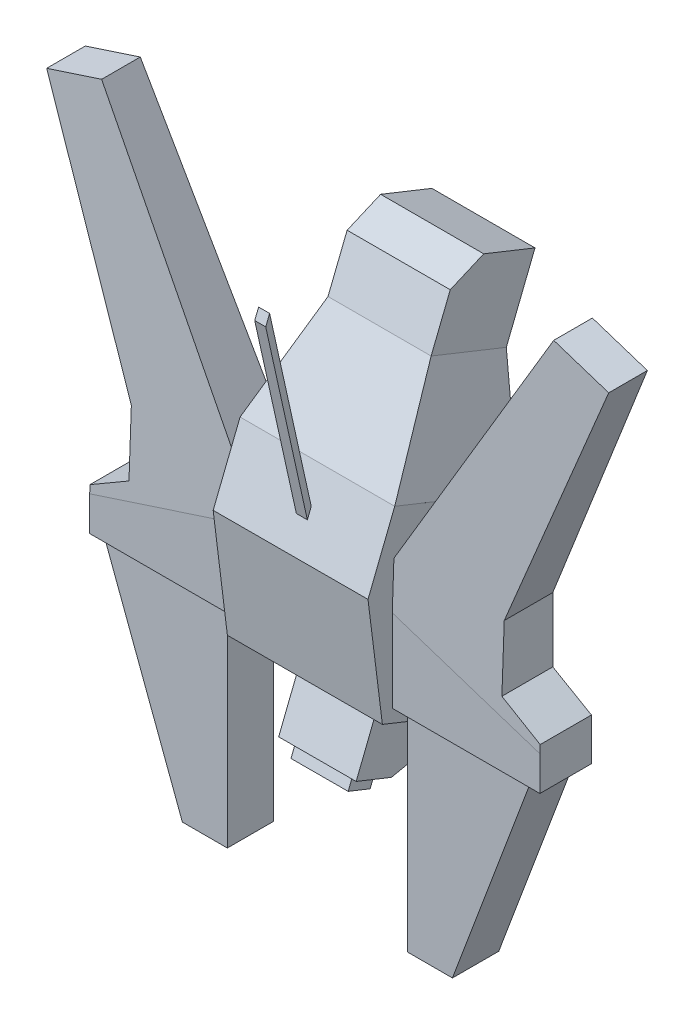
SolidWorks part; units mm, degrees
ref_plane "Front Plane" through (0, 0, 0) normal (0, 0, 1) x (1, 0, 0)
ref_plane "Top Plane" through (0, 0, 0) normal (0, 1, 0) x (1, 0, 0)
ref_plane "Right Plane" through (0, 0, 0) normal (1, 0, 0) x (0, 0, -1)
sketch "Sketch4" plane through (0, 0, 0) normal (0, 0, 1) x (1, 0, 0)
  line L0 (0, 0) -> (0, 12.7)
  line L1 (0, 12.7) -> (-14.6644, 38.1)
  line L2 (-14.6644, 38.1) -> (-20.0842, 36.3289)
  line L3 (-20.0842, 36.3289) -> (-10.7611, 12.7137)
  line L4 (-10.7611, 12.7137) -> (-10.7611, 6.3637)
  line L5 (-10.7611, 6.3637) -> (-14.5711, 4.164)
  line L6 (-14.5711, 4.164) -> (-14.5711, 0)
  line L7 (-14.5711, 0) -> (0, 0)
  dimension "D1" = 12.7
  dimension "D2" = 6.35
  dimension "D3" = 3.81
  dimension "D4" = 25.4
extrude "Boss-Extrude1" add sketch "Sketch4" along normal blind 5.08
chamfer "Chamfer5" distance 1.27 distance2 33.02 1 edges at (-17.3743, 37.2144, 5.08) first distance on face at (-17.3743, 37.2144, 2.54)
sketch "Sketch6" plane through (0, 0, 0) normal (0, -1, 0) x (1, 0, 0)
  line L0 (-7.2855, 0) -> (-7.2855, 5.08) construction
  line L1 (-14.5711, 0) -> (0, 0) construction
  line L2 (-14.5711, 5.08) -> (0, 5.08) construction
  line L4 (-13.312, 0.258) -> (-1.2591, 0.258)
  line L5 (-13.312, 0.258) -> (-13.312, 4.822)
  line L6 (-13.312, 4.822) -> (-1.2591, 4.822)
  line L7 (-1.2591, 0.258) -> (-1.2591, 4.822)
  line L8 (-13.312, 0.258) -> (-1.2591, 4.822) construction
  line L9 (-13.312, 4.822) -> (-1.2591, 0.258) construction
  point P6 (-7.2855, 2.54)
extrude "Boss-Extrude2" add sketch "Sketch6" along normal blind 20.32
chamfer "Chamfer6" distance 20.32 distance2 7.62 1 edges at (-13.312, -20.32, 2.54) first distance on face at (-13.312, -10.16, 2.54)
ref_plane "Plane2" through (7.62, 0, 0) normal (1, 0, 0) x (0, 0, -1)
mirror "Mirror8" about plane through (7.62, 0, 0) normal (1, 0, 0) of bodies 102
ref_axis "Axis2" through (7.62, 4.164, 0) along (0, -1, 0)
ref_plane "Plane4" through (0, 0, 0) normal (0, 0, 1) x (0, -1, 0)
sketch "Sketch7" plane through (0, 0, 0) normal (0, 0, 1) x (0, -1, 0)
  line L1 (5.0987, 0) -> (5.0987, 15.2803)
  line L4 (-20.2457, 15.24) -> (-20.2457, 0)
  line L6 (5.0987, 0) -> (-20.2457, 0)
  line L7 (-20.2457, 15.24) -> (5.0987, 15.2803)
extrude "Boss-Extrude5" add sketch "Sketch7" along normal mid plane 38.1 contours L1 L7 L4 L6
sketch "Sketch13" plane through (15.2721, 0.0243, 0) normal (1, 0.0016, 0) x (0, 0, -1)
  line L0 (-19.05, 4.2862) -> (4.4964, -5.1229)
  line L1 (-19.05, 20.2215) -> (-19.05, -5.1229) construction
  line L2 (-19.05, -5.1229) -> (19.05, -5.1229) construction
  line L3 (-19.05, 4.2862) -> (-19.05, -5.1229)
  line L4 (-19.05, -5.1229) -> (4.4964, -5.1229)
ref_plane "Plane6" through (0, -5.0987, 19.05) normal (1, 0, 0) x (0, 0, -1)
extrude "Cut-Extrude4" cut sketch "Sketch13" against normal blind 15.494 contours L3 L4 L0
sketch "Sketch18" plane through (0, -5.0987, 19.05) normal (1, 0, 0) x (0, 0, -1)
  line L0 (23.4857, 0) -> (0, 9.3849)
  line L1 (23.4857, 0) -> (33.6133, 25.3444)
  line L2 (0, 25.3444) -> (38.1, 25.3444) construction
  line L3 (23.4857, 0) -> (38.1, 0)
  line L4 (38.1, 0) -> (38.1, 25.3444)
  line L5 (38.1, 25.3444) -> (33.6133, 25.3444)
  dimension "D1" = 90
extrude "Cut-Extrude5" cut sketch "Sketch18" along normal blind 15.494 contours L4 L5 L1 L3 region at (0, 5.3338, -13.8273)
sketch "Sketch19" plane through (0, 0, 0) normal (-1, 0, 0) x (0, 0, 1)
  line L0 (19.05, 4.2863) -> (11.1889, 1.145)
  line L1 (-4.4357, -5.0987) -> (19.05, 4.2863) construction
  line L2 (19.05, 4.2863) -> (12.6726, 20.2457)
  line L3 (19.05, 20.2457) -> (-14.5633, 20.2457) construction
  line L4 (12.6726, 20.2457) -> (19.05, 20.2457)
  line L5 (19.05, 20.2457) -> (19.05, 4.2863)
  line M5 (19.05, 4.2863) -> (19.05, 20.2457)
  line M6 (19.05, 20.2457) -> (-14.5633, 20.2457)
  dimension "D1" = 90
extrude "Cut-Extrude6" cut sketch "Sketch19" against normal blind 15.494 contours L2 M5 M6 region at (0, 14.9259, 16.9242)
sketch "Sketch20" plane through (0, 0, 0) normal (-1, 0, 0) x (0, 0, 1)
  line L0 (12.6726, 20.2457) -> (16.227, 11.3507)
  line L1 (19.05, 4.2863) -> (12.6726, 20.2457) construction
  line L2 (12.6726, 20.2457) -> (-10.8131, 10.8608)
  line L3 (-4.4357, -5.0987) -> (-14.5633, 20.2457) construction
  line L4 (-10.8131, 10.8608) -> (-14.5633, 20.2457)
  line L5 (-14.5633, 20.2457) -> (12.6726, 20.2457)
  line M10 (12.6726, 20.2457) -> (-14.5633, 20.2457)
  line M11 (-14.5633, 20.2457) -> (-4.4357, -5.0987)
  dimension "D1" = 90
extrude "Cut-Extrude7" cut sketch "Sketch20" against normal blind 15.494 contours L2 M10 M11 region at (0, 17.1174, -4.2346)
chamfer "Chamfer7" distance 25.4 distance2 13.97 1 edges at (7.6327, 4.2967, 19.0458) first distance on face at (7.6263, 12.2712, 15.8592)
sketch "Sketch21" plane through (0, 0, 0) normal (-1, 0, 0) x (0, 0, 1)
  line L0 (8.4777, 18.5694) -> (4.8258, 17.1101)
  line L1 (8.4777, 18.5694) -> (-10.8131, 10.8608) construction
  line L2 (4.8258, 17.1101) -> (7.4791, 10.4703)
  line L3 (6.0774, -0.8976) -> (8.4777, 18.5694) construction
  line L4 (7.4791, 10.4703) -> (8.4777, 18.5694)
extrude "Cut-Extrude9" cut sketch "Sketch21" against normal blind 15.494 contours L4 L0 L2
sketch "Sketch22" plane through (0.0046, -2.8682, 1.1461) normal (0.0015, -0.9286, 0.3711) x (1, 0.0014, -0.0005)
  line L0 (15.2757, -6.011) -> (-0.0046, -6.011) construction
  line L11 (7.6356, -6.011) -> (11.537, -6.011)
  line L12 (11.537, -6.011) -> (11.537, 1.5466)
  line L13 (11.537, 1.5466) -> (3.9, 1.5466)
  line L14 (3.9, 1.5466) -> (3.9, -6.011)
  line L15 (3.9, -6.011) -> (7.6356, -6.011)
extrude "Boss-Extrude7" add sketch "Sketch22" along normal blind 6.35
sketch "Sketch24" plane through (0.0046, -2.8682, 1.1461) normal (0.0015, -0.9286, 0.3711) x (1, 0.0014, -0.0005)
  line L0 (11.537, -6.011) -> (11.537, 1.5466) construction
  line L1 (15.2757, -6.011) -> (11.537, -6.011)
  line L2 (15.2757, -6.011) -> (15.2757, -2.2322)
  line L3 (15.2757, -2.2322) -> (11.537, -2.2322)
  line L4 (11.537, -6.011) -> (11.537, -2.2322)
  line L5 (3.9, 1.5466) -> (3.9, -6.011) construction
  line L6 (-0.0046, -6.011) -> (3.9, -6.011)
  line L7 (-0.0046, -6.011) -> (-0.0046, -2.2322)
  line L8 (-0.0046, -2.2322) -> (3.9, -2.2322)
  line L9 (3.9, -6.011) -> (3.9, -2.2322)
extrude "Cut-Extrude11" cut sketch "Sketch24" against normal blind 19.05
chamfer "Chamfer9" distance 2.54 distance2 3.81 1 edges at (7.7324, -10.9847, -2.0836) first distance on face at (7.7151, -0.062, -6.4483)
sketch "Sketch25" plane through (0, 13.0913, -5.2313) normal (0, 0.9286, -0.3711) x (1, 0, 0)
  line L0 (11.5162, 6.011) -> (11.5162, 4.6398)
  line L1 (11.5162, 6.011) -> (11.5162, 2.2322) construction
  line L2 (11.5162, 4.6398) -> (3.8792, 4.6398)
  line L3 (3.8792, 2.2322) -> (3.8792, 6.011) construction
  line L4 (3.8792, 4.6398) -> (3.8792, 6.011)
  line L5 (3.8792, 6.011) -> (11.5162, 6.011)
sketch "Sketch26" plane through (0, -2.2305, -5.5818) normal (0, -0.3711, -0.9286) x (-1, 0, 0)
  line L1 (-19.1145, 20.3372) -> (4.2562, 20.3372)
  line L2 (-19.1145, 20.3372) -> (-19.1145, -11.1637)
  line L3 (-19.1145, -11.1637) -> (4.2562, -11.1637)
  line L4 (4.2562, 20.3372) -> (4.2562, -11.1637)
extrude "Cut-Extrude14" cut sketch "Sketch26" against normal blind 1.27
sketch "Sketch27" plane through (0.0139, -8.7648, 3.5024) normal (0.0015, -0.9286, 0.3711) x (1, 0.0014, -0.0005)
  line L0 (7.7185, -2.201) -> (7.7185, 1.493) construction
  line L1 (3.9, -2.201) -> (11.537, -2.201) construction
  line L3 (4.902, -1.5184) -> (10.535, -1.5184)
  line L4 (4.902, -1.5184) -> (4.902, 0.8104)
  line L5 (4.902, 0.8104) -> (10.535, 0.8104)
  line L6 (10.535, -1.5184) -> (10.535, 0.8104)
  line L7 (4.902, -1.5184) -> (10.535, 0.8104) construction
  line L8 (4.902, 0.8104) -> (10.535, -1.5184) construction
  point P4 (7.7185, -0.354)
extrude "Boss-Extrude9" add sketch "Sketch27" along normal blind 1.27
ref_plane "Plane7" through (0, 4.0188, 10.0571) normal (0, 0.3711, 0.9286) x (1, 0, 0)
ref_plane "Plane8" through (7.62, -5.0987, 19.05) normal (1, 0, 0) x (0, 0, -1)
sketch "Sketch30" plane through (0, 4.0188, 10.0571) normal (0, 0.3711, 0.9286) x (1, 0, 0)
  line L5 (7.3575, 10.6628) -> (7.9441, 10.1578) construction
  line L6 (7.3575, 10.1578) -> (7.9441, 10.6628) construction
  line L7 (7.1085, 9.8938) -> (8.193, 9.8938)
  line L8 (7.1085, 9.8938) -> (7.1085, 10.9267)
  line L9 (7.1085, 10.9267) -> (8.193, 10.9267)
  line L10 (8.193, 9.8938) -> (8.193, 10.9267)
  line L11 (7.1085, 9.8938) -> (8.193, 10.9267) construction
  line L12 (7.1085, 10.9267) -> (8.193, 9.8938) construction
  point P0 (7.6508, 10.4103)
  point P5 (7.6508, 10.4103)
  dimension "D1" = 0.505
sketch "Sketch31" plane through (7.62, -5.0987, 19.05) normal (1, 0, 0) x (0, 0, -1)
  line L0 (12.8613, 18.7822) -> (8.7545, 37.3195)
sweep "Sweep3" add profiles "Sketch30" path "Sketch31"
ref_plane "Plane9" through (0, -1.7592, -4.4025) normal (0, -0.3711, -0.9286) x (-1, 0, 0)
sketch "Sketch33" plane through (0, -1.7592, -4.4025) normal (0, -0.3711, -0.9286) x (-1, 0, 0)
  line L1 (-3.9114, -7.7396) -> (-11.5162, -7.7396)
  line L2 (-3.9114, -7.7396) -> (-3.9114, 14.0978)
  line L3 (-3.9114, 14.0978) -> (-11.5162, 14.0978)
  line L4 (-11.5162, -7.7396) -> (-11.5162, 14.0978)
  dimension "D1" = 21.8374
  dimension "D2" = 7.6048
ref_plane "Plane10" through (0, 13.0913, -5.2313) normal (0, 0.9286, -0.3711) x (1, 0, 0)
sketch "Sketch34" plane through (0, 13.0913, -5.2313) normal (0, 0.9286, -0.3711) x (1, 0, 0)
  line L1 (15.245, -10.8303) -> (0, -10.8303)
  line L2 (15.245, -10.8303) -> (15.245, 2.2322)
  line L3 (15.245, 2.2322) -> (0, 2.2322)
  line L4 (0, -10.8303) -> (0, 2.2322)
extrude "Boss-Extrude14" add sketch "Sketch34" along normal blind 10.16 contours L1 L4 L3 L2
chamfer "Chamfer11" distance 2.54 distance2 10.16 4 edges at (15.245, 24.1211, -5.0093) (7.6225, 21.6976, -11.0742) (0, 24.1211, -5.0093) (7.6225, 26.5447, 1.0557) first distance on face at (7.6225, 24.1211, -5.0093)
sketch "Sketch38" plane through (0, 22.5259, -9.0014) normal (0, 0.9286, -0.3711) x (1, 0, 0)
  line L1 (2.54, -8.2903) -> (12.705, -8.2903)
  line L2 (2.54, -8.2903) -> (2.54, -0.3078)
  line L3 (2.54, -0.3078) -> (12.705, -0.3078)
  line L4 (12.705, -8.2903) -> (12.705, -0.3078)
extrude "Boss-Extrude15" add sketch "Sketch38" along normal blind 7.62
chamfer "Chamfer12" distance 2.54 angle 45 1 edges at (7.6225, 32.6781, -4.1305)
extrude "Boss-Extrude16" [suppressed] add sketch "Sketch33" along normal blind 10.16 contours L2 L3 L4 L1
